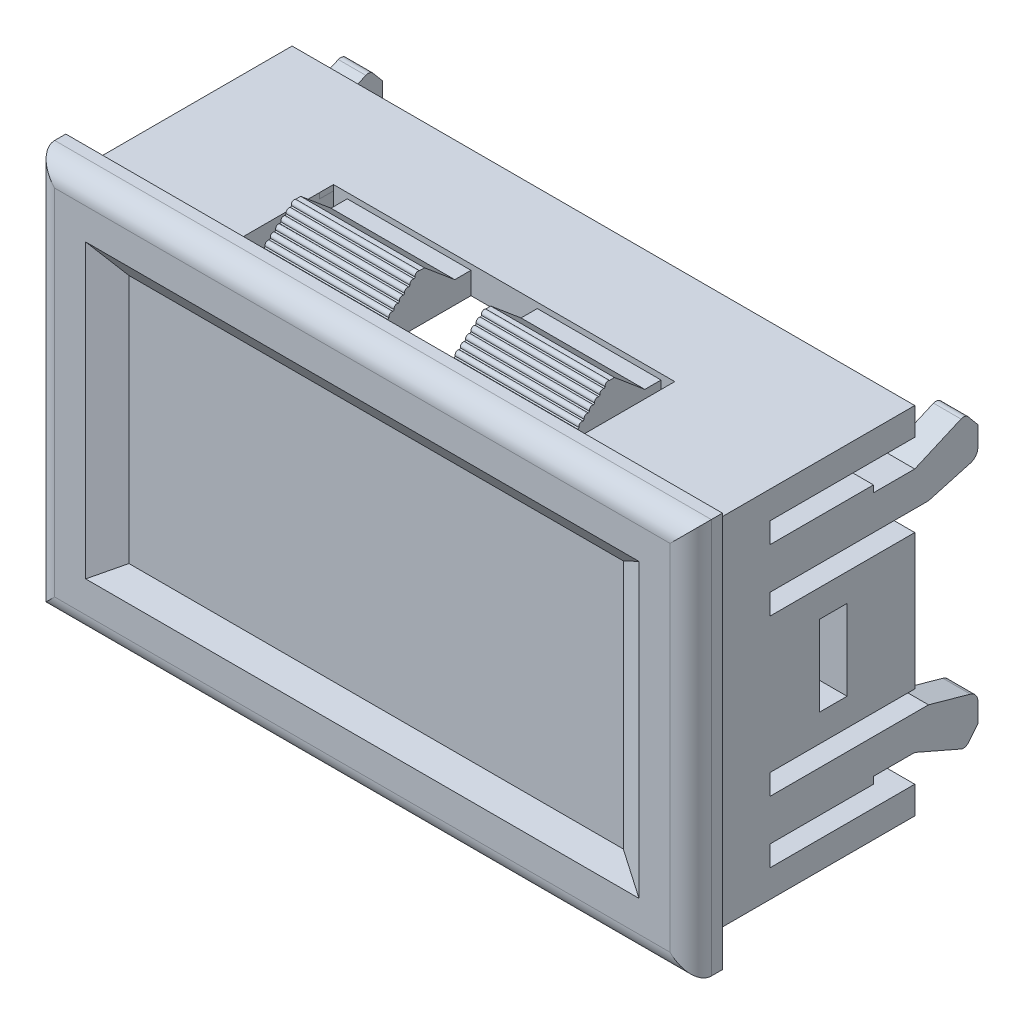
SolidWorks part; units mm, degrees
ref_plane "Plano frontal" through (0, 0, 0) normal (0, 0, 1) x (1, 0, 0)
ref_plane "Plano superior" through (0, 0, 0) normal (0, 1, 0) x (1, 0, 0)
ref_plane "Plano direito" through (0, 0, 0) normal (1, 0, 0) x (0, 0, -1)
sketch "Esboço1" plane through (0, 0, 0) normal (0, 0, 1) x (1, 0, 0)
  line L1 (23.875, -14.375) -> (-23.875, -14.375)
  line L2 (23.875, -14.375) -> (23.875, 14.375)
  line L3 (23.875, 14.375) -> (-23.875, 14.375)
  line L4 (-23.875, -14.375) -> (-23.875, 14.375)
  line L5 (23.875, -14.375) -> (-23.875, 14.375) construction
  line L6 (23.875, 14.375) -> (-23.875, -14.375) construction
  point P0 (0, 0)
  dimension "D1" = 47.75
  dimension "D2" = 28.75
extrude "Ressalto-extrusão1" add sketch "Esboço1" along normal blind 17.53
sketch "Esboço3" plane through (0, 0, 0) normal (0, 0, -1) x (-1, 0, 0)
  line L1 (-22.64, -12.925) -> (22.64, -12.925)
  line L2 (-22.64, -12.925) -> (-22.64, 12.925)
  line L3 (-22.64, 12.925) -> (22.64, 12.925)
  line L4 (22.64, -12.925) -> (22.64, 12.925)
  line L5 (-22.64, -12.925) -> (22.64, 12.925) construction
  line L6 (-22.64, 12.925) -> (22.64, -12.925) construction
  line L7 (-27.5567, -16.1162) -> (27.5567, -16.1162)
  line L8 (-27.5567, -16.1162) -> (-27.5567, 16.1162)
  line L9 (-27.5567, 16.1162) -> (27.5567, 16.1162)
  line L10 (27.5567, -16.1162) -> (27.5567, 16.1162)
  line L11 (-27.5567, -16.1162) -> (27.5567, 16.1162) construction
  line L12 (-27.5567, 16.1162) -> (27.5567, -16.1162) construction
  point P0 (0, 0)
  point P6 (0, 0)
  dimension "D1" = 25.85
  dimension "D2" = 45.28
extrude "Corte-extrusão1" cut sketch "Esboço3" against normal blind 15.22
sketch "Esboço4" plane through (0, 0, 17.53) normal (0, 0, 1) x (1, 0, 0)
  line L1 (-17.975, -9.07) -> (17.975, -9.07)
  line L2 (-17.975, -9.07) -> (-17.975, 9.07)
  line L3 (-17.975, 9.07) -> (17.975, 9.07)
  line L4 (17.975, -9.07) -> (17.975, 9.07)
  line L5 (-17.975, -9.07) -> (17.975, 9.07) construction
  line L6 (-17.975, 9.07) -> (17.975, -9.07) construction
  point P0 (0, 0)
  dimension "D1" = 18.14
  dimension "D2" = 35.95
extrude "Corte-extrusão2" cut sketch "Esboço4" against normal blind 33.22 and the other way blind 17
sketch "Esboço5" plane through (0, 0, 0) normal (0, 0, -1) x (-1, 0, 0)
  line L5 (20.64, -10.925) -> (-20.64, -10.925)
  line L6 (20.64, -10.925) -> (20.64, 10.925)
  line L7 (20.64, 10.925) -> (-20.64, 10.925)
  line L8 (-20.64, -10.925) -> (-20.64, 10.925)
  line L9 (20.64, -10.925) -> (-20.64, 10.925) construction
  line L10 (20.64, 10.925) -> (-20.64, -10.925) construction
  point P9 (0, 0)
extrude "Corte-extrusão3" cut sketch "Esboço5" against normal blind 15.22
chamfer "Chanfro1" distance 1 angle 65 1 edges at (17.975, 0, 17.53)
chamfer "Chanfro2" distance 1 angle 65 1 edges at (-17.975, 0, 17.53)
chamfer "Chanfro3" distance 1 angle 57 2 edges at (0, -9.07, 17.53) (0, 9.07, 17.53)
fillet "Filete1" radius 1.5 4 edges at (23.875, 0, 17.53) (-23.875, 0, 17.53) (0, -14.375, 17.53) (0, 14.375, 17.53)
sketch "Esboço6" plane through (0, 12.925, 0) normal (0, 1, 0) x (1, 0, 0)
  line L0 (-11.41, -7.8955) -> (-11.41, -7.22)
  line L2 (-22.64, -15.22) -> (22.64, -15.22) construction
  line L3 (-12.41, -7.22) -> (-11.41, -7.22)
  line L4 (-12.41, -7.22) -> (-12.41, -15.22)
  line L5 (-12.41, -15.22) -> (12.41, -15.22)
  line L6 (12.41, -7.22) -> (12.41, -15.22)
  line L7 (2.41, -14.5445) -> (11.41, -14.5445)
  line L8 (-2.41, -7.22) -> (2.41, -7.22)
  line L9 (2.41, -7.22) -> (2.41, -14.5445)
  line L10 (-11.41, -14.5445) -> (-2.41, -14.5445)
  line L11 (-11.41, -14.5445) -> (-11.41, -7.8955)
  line L12 (11.41, -7.22) -> (12.41, -7.22)
  line L13 (11.41, -14.5445) -> (11.41, -7.8955)
  line L16 (-2.41, -7.22) -> (-2.41, -14.5445)
  line L18 (11.41, -7.8955) -> (11.41, -7.22)
  point P5 (0, -11.22)
  point P12 (0, -11.22)
  dimension "D1" = 24.82
  dimension "D2" = 8
  dimension "D3" = 1
  dimension "D4" = 9
  dimension "D5" = 9
extrude "Corte-extrusão4" cut sketch "Esboço6" against normal blind 44.22 and the other way blind 15
sketch "Esboço7" plane through (0, 12.925, 0) normal (0, 1, 0) x (1, 0, 0)
  line L0 (-2.41, -7.22) -> (2.41, -7.22) construction
  line L1 (-12.4101, -8.22) -> (12.4101, -8.22)
  line L2 (12.4101, -8.22) -> (12.41, -7.22)
  line L3 (-12.4101, -8.22) -> (-12.41, -7.22)
  line L5 (-12.41, -7.22) -> (12.41, -7.22)
  point P0 (0, -7.22)
  dimension "D1" = 1
extrude "Corte-extrusão5" cut sketch "Esboço7" against normal blind 0.4
sketch "Esboço8" plane through (0, -12.925, 0) normal (0, -1, 0) x (1, 0, 0)
  line L0 (-12.41, 8.22) -> (12.41, 8.22)
  line L1 (12.41, 8.22) -> (12.41, 7.22)
  line L2 (12.41, 7.22) -> (-12.41, 7.22)
  line L3 (-12.41, 7.22) -> (-12.41, 8.22)
extrude "Corte-extrusão6" cut sketch "Esboço8" against normal blind 0.4
sketch "Esboço9" plane through (0, 12.925, 0) normal (0, 1, 0) x (1, 0, 0)
  line L2 (-11.41, -14.5445) -> (-2.41, -14.5445) construction
  line L3 (-2.41, -14.5445) -> (-2.41, -8.22) construction
  line L4 (-11.41, -8.22) -> (-2.41, -8.22)
  line L5 (-11.41, -8.22) -> (-11.41, -14.5445)
  line L6 (-11.41, -14.5445) -> (-2.41, -14.5445)
  line L7 (-2.41, -8.22) -> (-2.41, -14.5445)
  line L8 (-11.41, -8.22) -> (-2.41, -14.5445) construction
  line L9 (-11.41, -14.5445) -> (-2.41, -8.22) construction
  point P6 (-6.91, -11.3822)
extrude "Ressalto-extrusão2" add sketch "Esboço9" along normal blind 1.45
sketch "Esboço10" plane through (0, 12.925, 0) normal (0, 1, 0) x (1, 0, 0)
  line L4 (2.41, -14.5445) -> (11.41, -14.5445)
  line L5 (2.41, -14.5445) -> (2.41, -8.22)
  line L6 (2.41, -8.22) -> (11.41, -8.22)
  line L7 (11.41, -14.5445) -> (11.41, -8.22)
  line L8 (2.41, -14.5445) -> (11.41, -8.22) construction
  line L9 (2.41, -8.22) -> (11.41, -14.5445) construction
  point P6 (6.91, -11.3822)
extrude "Ressalto-extrusão3" add sketch "Esboço10" along normal blind 1.45
sketch "Esboço11" plane through (0, -12.925, 0) normal (0, -1, 0) x (1, 0, 0)
  line L3 (-6.91, 11.3822) -> (-6.91, 14.5445)
  line L5 (-2.41, 14.5445) -> (-11.41, 14.5445) construction
  line L7 (11.41, 14.5445) -> (2.41, 14.5445)
  line L8 (11.41, 14.5445) -> (11.41, 8.22)
  line L9 (11.41, 8.22) -> (2.41, 8.22)
  line L10 (2.41, 14.5445) -> (2.41, 8.22)
  line L11 (11.41, 14.5445) -> (2.41, 8.22) construction
  line L12 (11.41, 8.22) -> (2.41, 14.5445) construction
  line L13 (-2.41, 14.5445) -> (-11.41, 14.5445)
  line L14 (-2.41, 14.5445) -> (-2.41, 8.22)
  line L15 (-2.41, 8.22) -> (-11.41, 8.22)
  line L16 (-11.41, 14.5445) -> (-11.41, 8.22)
  line L17 (-2.41, 14.5445) -> (-11.41, 8.22) construction
  line L18 (-2.41, 8.22) -> (-11.41, 14.5445) construction
  point P12 (6.91, 11.3822)
  point P18 (-6.91, 11.3822)
extrude "Ressalto-extrusão4" add sketch "Esboço11" along normal blind 1.45
chamfer "Chanfro4" distance 3 angle 50 4 edges at (-6.91, 14.375, 14.5445) (6.91, 14.375, 14.5445) (6.91, -14.375, 14.5445) (-6.91, -14.375, 14.5445)
chamfer "Chanfro5" distance 2 angle 50 16 edges at (-2.41, 13.45, 8.22) (2.41, 13.45, 8.22) (-11.41, 13.45, 8.22) (11.41, 13.45, 8.22) (-6.91, 12.525, 8.22) (6.91, 12.525, 8.22) (-2.41, -13.45, 8.22) (2.41, -13.45, 8.22) (11.41, -13.45, 8.22) (-11.41, -13.45, 8.22) (6.91, -12.525, 8.22) (-6.91, -12.525, 8.22) (-6.91, 14.375, 8.22) (6.91, 14.375, 8.22) (6.91, -14.375, 8.22) (-6.91, -14.375, 8.22)
sketch "Esboço13" plane through (-11.41, 0, 0) normal (-1, 0, 0) x (0, 0, 1)
  line L0 (11.2735, 14.1196) -> (10.9692, 14.375)
  line L1 (14.5445, 11.375) -> (10.9692, 14.375) construction
  line L2 (11.3522, 14.0536) -> (11.6566, 13.7982)
  line L3 (11.7353, 13.7322) -> (12.0396, 13.4769)
  line L4 (12.1183, 13.4108) -> (12.4226, 13.1555)
  line L5 (12.5013, 13.0894) -> (12.8056, 12.8341)
  line L6 (12.8843, 12.768) -> (13.1887, 12.5127)
  line L7 (13.2674, 12.4466) -> (13.5717, 12.1913)
  line L8 (13.6504, 12.1252) -> (13.9547, 11.8699)
  line L9 (14.0334, 11.8038) -> (14.3377, 11.5485)
  arc A0 (10.9692, 14.375) -> (11.2735, 14.1196) centre (11.0708, 14.187) cw
  arc A1 (11.3522, 14.0536) -> (11.6566, 13.7982) centre (11.4538, 13.8656) cw
  arc A2 (11.7353, 13.7322) -> (12.0396, 13.4769) centre (11.8368, 13.5442) cw
  arc A3 (12.1183, 13.4108) -> (12.4226, 13.1555) centre (12.2198, 13.2228) cw
  arc A4 (12.5013, 13.0894) -> (12.8056, 12.8341) centre (12.6029, 12.9014) cw
  arc A5 (12.8843, 12.768) -> (13.1887, 12.5127) centre (12.9859, 12.58) cw
  arc A6 (13.2674, 12.4466) -> (13.5717, 12.1913) centre (13.3689, 12.2587) cw
  arc A7 (13.6504, 12.1252) -> (13.9547, 11.8699) centre (13.7519, 11.9373) cw
  arc A8 (14.0334, 11.8038) -> (14.3377, 11.5485) centre (14.135, 11.6159) cw
  dimension "D1" = 9
extrude "Ressalto-extrusão5" add sketch "Esboço13" against normal blind 22.82
sketch "Esboço15" plane through (0, -12.925, 0) normal (0, -1, 0) x (1, 0, 0)
  line L0 (-2.41, 14.5445) -> (-2.41, 10.9692)
  line L1 (-2.41, 10.9692) -> (2.41, 10.9692)
  line L2 (2.41, 10.9692) -> (2.41, 14.5445)
  line L3 (2.41, 14.5445) -> (-2.41, 14.5445)
extrude "Corte-extrusão9" cut sketch "Esboço15" against normal blind 35.82 and the other way blind 16
sketch "Esboço16" plane through (11.41, 0, 0) normal (1, 0, 0) x (0, 0, -1)
  line L0 (-10.6035, -14.375) -> (-8.8845, -12.9326)
  line L1 (-10.6035, -14.375) -> (-8.3988, -12.525) construction
  line L2 (-8.8845, -12.9326) -> (-8.7241, -13.1582)
  line L3 (-8.7241, -13.1582) -> (-10.1324, -14.7684)
  line L4 (-10.1324, -14.7684) -> (-10.6035, -14.375)
extrude "Corte-extrusão10" cut sketch "Esboço16" against normal blind 22.82
sketch "Esboço18" plane through (11.41, 0, 0) normal (1, 0, 0) x (0, 0, -1)
  line L0 (-8.3988, -12.525) -> (-10.6035, -14.375)
  line L1 (-10.6035, -14.375) -> (-10.9886, -13.916)
  line L2 (-10.9886, -13.916) -> (-8.7449, -12.0333)
  line L3 (-8.7449, -12.0333) -> (-8.3988, -12.525)
extrude "Ressalto-extrusão6" add sketch "Esboço18" against normal blind 9
sketch "Esboço19" plane through (-11.41, 0, 0) normal (-1, 0, 0) x (0, 0, 1)
  line L0 (8.3988, -12.525) -> (10.6035, -14.375)
  line L1 (10.6035, -14.375) -> (10.6873, -14.2752)
  line L2 (10.6873, -14.2752) -> (8.7036, -12.4713)
  line L3 (8.7036, -12.4713) -> (8.3988, -12.525)
extrude "Ressalto-extrusão8" add sketch "Esboço19" against normal blind 9
sketch "Esboço20" plane through (11.41, 0, 0) normal (1, 0, 0) x (0, 0, -1)
  line L0 (-10.9692, -14.375) -> (-11.291, -14.105)
  line L1 (-14.5445, -11.375) -> (-10.9692, -14.375) construction
  line L2 (-11.3522, -14.0536) -> (-11.674, -13.7836)
  line L3 (-11.7353, -13.7322) -> (-12.057, -13.4622)
  line L4 (-12.1183, -13.4108) -> (-12.44, -13.1408)
  line L5 (-12.5013, -13.0894) -> (-12.823, -12.8195)
  line L6 (-12.8843, -12.768) -> (-13.2061, -12.4981)
  line L7 (-13.2674, -12.4466) -> (-13.5891, -12.1767)
  line L8 (-13.6504, -12.1252) -> (-13.9721, -11.8553)
  line L9 (-14.0334, -11.8038) -> (-14.3551, -11.5339)
  arc A0 (-11.291, -14.105) -> (-10.9692, -14.375) centre (-11.106, -14.2113) ccw
  arc A2 (-11.674, -13.7836) -> (-11.3522, -14.0536) centre (-11.4891, -13.89) ccw
  arc A3 (-12.057, -13.4622) -> (-11.7353, -13.7322) centre (-11.8721, -13.5686) ccw
  arc A4 (-12.44, -13.1408) -> (-12.1183, -13.4108) centre (-12.2551, -13.2472) ccw
  arc A5 (-12.823, -12.8195) -> (-12.5013, -13.0894) centre (-12.6381, -12.9258) ccw
  arc A6 (-13.2061, -12.4981) -> (-12.8843, -12.768) centre (-13.0211, -12.6044) ccw
  arc A7 (-13.5891, -12.1767) -> (-13.2674, -12.4466) centre (-13.4042, -12.283) ccw
  arc A8 (-13.9721, -11.8553) -> (-13.6504, -12.1252) centre (-13.7872, -11.9616) ccw
  arc A9 (-14.3551, -11.5339) -> (-14.0334, -11.8038) centre (-14.1702, -11.6402) ccw
  dimension "D2" = 9
  dimension "D1" = 0.42
extrude "Ressalto-extrusão9" add sketch "Esboço20" against normal blind 22.82
sketch "Esboço21" plane through (0, -12.925, 0) normal (0, -1, 0) x (1, 0, 0)
  line L4 (-2.41, 10.8083) -> (2.41, 10.8083)
  line L5 (-2.41, 10.8083) -> (-2.41, 14.5445)
  line L6 (-2.41, 14.5445) -> (2.41, 14.5445)
  line L7 (2.41, 10.8083) -> (2.41, 14.5445)
  line L8 (-2.41, 10.8083) -> (2.41, 14.5445) construction
  line L9 (-2.41, 14.5445) -> (2.41, 10.8083) construction
  point P6 (0, 12.6764)
extrude "Corte-extrusão11" cut sketch "Esboço21" against normal blind 22.82
sketch "Esboço22" plane through (0, -12.925, 0) normal (0, -1, 0) x (1, 0, 0)
  line L0 (-2.41, 14.5445) -> (-2.41, 10.9692)
  line L1 (-2.41, 10.9692) -> (2.41, 10.9692)
  line L2 (2.41, 10.9692) -> (2.41, 14.5445)
  line L3 (2.41, 14.5445) -> (-2.41, 14.5445)
extrude "Corte-extrusão13" cut sketch "Esboço22" against normal blind 22.82 and the other way blind 20
sketch "Esboço23" plane through (22.64, 0, 0) normal (1, 0, 0) x (0, 0, -1)
  line L0 (-6.92, 2.925) -> (-4.92, 2.925)
  line L1 (0, -10.925) -> (-10.53, -10.925)
  line L2 (-10.53, -6.425) -> (-10.53, -4.925)
  line L3 (-10.53, 10.925) -> (0, 10.925)
  line L4 (-10.53, -10.925) -> (-10.53, -9.425)
  line L5 (0, -4.925) -> (0, -6.425)
  line L6 (-10.53, 9.425) -> (-10.53, 10.925)
  line L7 (0, 10.925) -> (0, 9.425)
  line L9 (-10.53, 9.425) -> (0, 9.425)
  line L10 (-10.53, -9.425) -> (0, -9.425)
  line L11 (0, 6.425) -> (0, 4.925)
  line L12 (-10.53, 4.925) -> (-10.53, 6.425)
  line L13 (0, -9.425) -> (0, -10.925)
  line L14 (-10.53, -6.425) -> (0, -6.425)
  line L15 (-6.92, -2.925) -> (-4.92, -2.925)
  line L16 (-10.53, 6.425) -> (0, 6.425)
  line L18 (-4.92, 2.925) -> (-4.92, -2.925)
  line L19 (-6.92, 2.925) -> (-6.92, -2.925)
  line L22 (-10.53, -4.925) -> (0, -4.925)
  line L24 (-10.53, 4.925) -> (0, 4.925)
  point P0 (0, 0)
  point P19 (-5.265, 4.925)
  point P20 (0, 0)
  point P25 (0, 0)
  dimension "D1" = 2
  dimension "D3" = 1.5
  dimension "D5" = 2
extrude "Corte-extrusão14" cut sketch "Esboço23" against normal blind 62.82
sketch "Esboço24" plane through (22.64, 0, 0) normal (1, 0, 0) x (0, 0, -1)
  line L0 (0, 9.425) -> (-3, 9.425)
  line L1 (-10.53, 9.425) -> (0, 9.425) construction
  line L2 (-3, 9.425) -> (-3, 8.929)
  line L3 (-3, -8.925) -> (-3, -9.425)
  line L4 (-3, 8.929) -> (0, 8.929)
  line L5 (0, 9.425) -> (0, 6.425) construction
  line L6 (0, 8.929) -> (0, 9.425)
  line L7 (0, -9.425) -> (-10.53, -9.425) construction
  line L8 (-3, -9.425) -> (0, -9.425)
  line L9 (0, -9.425) -> (0, -8.925)
  line L10 (0, -6.425) -> (0, -9.425) construction
  line L11 (0, -8.925) -> (-3, -8.925)
  dimension "D1" = 3
  dimension "D2" = 0.5
extrude "Corte-extrusão15" cut sketch "Esboço24" against normal blind 62.82
sketch "Esboço25" plane through (22.64, 0, 0) normal (1, 0, 0) x (0, 0, -1)
  line L0 (0, 8.929) -> (0, 6.425)
  line L1 (0, 6.425) -> (-0.0205, 6.5266)
  line L2 (-3, 8.929) -> (0, 8.929) construction
  line L3 (0, 6.425) -> (1, 6.425)
  line L4 (0, 8.929) -> (3.3636, 10.3917)
  line L5 (1, 6.425) -> (4.0413, 7.2721)
  line L6 (4.59, 9.425) -> (4.59, 7.9946)
  line L7 (0, -8.925) -> (0, -6.425)
  line L8 (3.8888, 10.267) -> (4.59, 9.425)
  line L9 (0, -8.925) -> (3.3638, -10.3907)
  line L10 (0, -6.425) -> (1, -6.425)
  line L11 (4.59, -9.425) -> (4.59, -7.9946)
  line L12 (4.0413, -7.2721) -> (1, -6.425)
  line L14 (4.59, -9.425) -> (3.8893, -10.2662)
  arc A0 (4.59, 7.9946) -> (4.0413, 7.2721) centre (3.84, 7.9946) cw
  arc A1 (4.59, -7.9946) -> (4.0413, -7.2721) centre (3.84, -7.9946) ccw
  arc A2 (3.8888, 10.267) -> (3.3636, 10.3917) centre (3.543, 9.979) ccw
  arc A3 (3.8893, -10.2662) -> (3.3638, -10.3907) centre (3.5435, -9.9782) cw
  point P1 (4.59, 10.925)
  point P11 (4.59, -10.925)
  point P13 (4.59, 7.425)
  point P24 (4.59, -7.425)
  point P27 (3.673, 10.5262)
  point P30 (3.6732, -10.5255)
  line M8 (0, -8.925) -> (0, -6.425)
  line M16 (0, 6.425) -> (0, 8.929)
  dimension "D1" = 0.75
  dimension "D5" = 0.45
  dimension "D2" = 1
  dimension "D3" = 3.5
  dimension "D4" = 3.5
  dimension "D8" = 1
  dimension "D9" = 1
extrude "Ressalto-extrusão10" add sketch "Esboço25" against normal blind 45.28 contours L8 A2 L4 L3 L5 A0 L6 M16 | A3 L14 L11 A1 L12 L10 L9 M8
sketch "Esboço26" plane through (0, 0, 15.22) normal (0, 0, -1) x (-1, 0, 0)
  line L1 (-20.64, -10.925) -> (20.64, -10.925)
  line L2 (-20.64, -10.925) -> (-20.64, 10.925)
  line L3 (-20.64, 10.925) -> (20.64, 10.925)
  line L4 (20.64, -10.925) -> (20.64, 10.925)
  line L5 (-20.64, -10.925) -> (20.64, 10.925) construction
  line L6 (-20.64, 10.925) -> (20.64, -10.925) construction
  point P0 (0, 0)
extrude "Corte-extrusão16" cut sketch "Esboço26" along normal blind 41.28
sketch "Sketch1" plane through (-17.975, 0, 0) normal (1, 0, 0) x (0, 0, -1)
  line L0 (-15.22, -9.07) -> (-15.22, 9.07) construction
  line L1 (-16.53, 9.07) -> (-15.22, 9.07)
  line L2 (-16.53, 9.07) -> (-16.53, -9.07)
  line L3 (-16.53, -9.07) -> (-15.22, -9.07)
  line L4 (-15.22, 9.07) -> (-15.22, -9.07)
extrude "Boss-Extrude1" add sketch "Sketch1" along normal up to surface (35.95 mm away)
